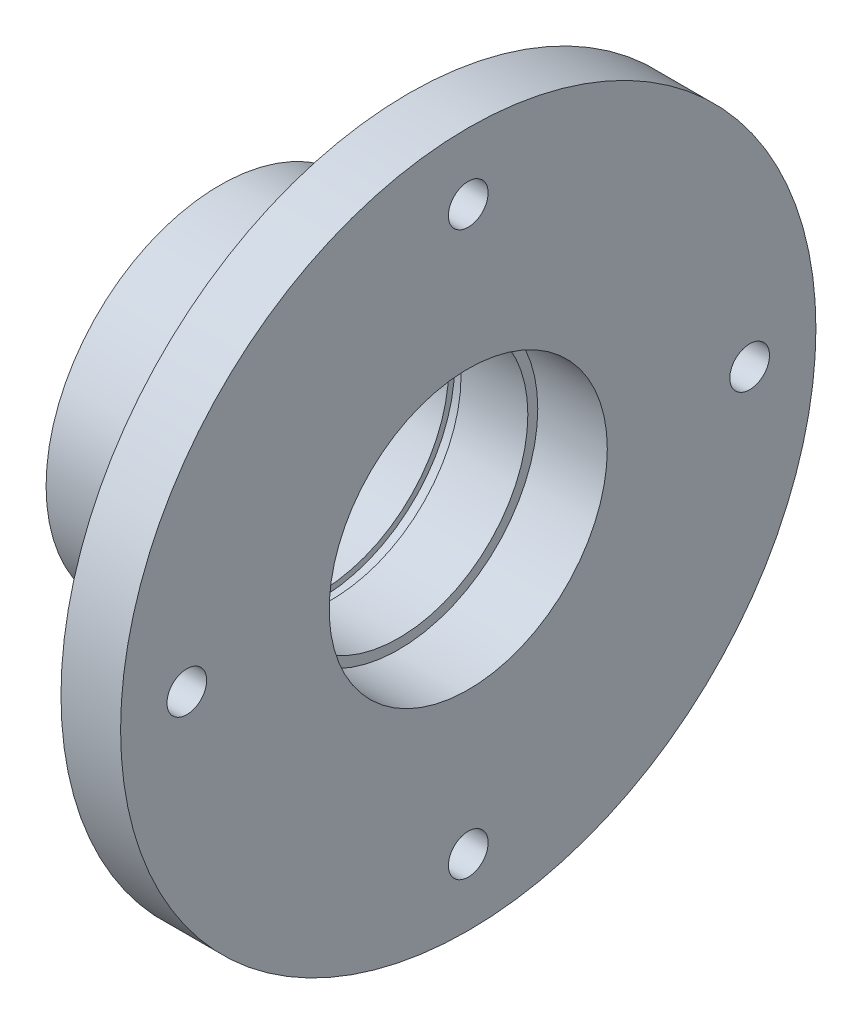
SolidWorks part; units mm, degrees
ref_plane "Front Plane" through (0, 0, 0) normal (0, 0, 1) x (1, 0, 0)
ref_plane "Top Plane" through (0, 0, 0) normal (0, 1, 0) x (1, 0, 0)
ref_plane "Right Plane" through (0, 0, 0) normal (1, 0, 0) x (0, 0, -1)
sketch "Sketch1" plane through (0, 0, 0) normal (1, 0, 0) x (0, 0, -1)
  circle A0 centre (0, 0) radius 35
extrude "Boss-Extrude1" add sketch "Sketch1" against normal blind 25
sketch "Sketch2" plane through (-25, 0, 0) normal (-1, 0, 0) x (0, 0, 1)
  circle A0 centre (0, 0) radius 17.5
  circle A1 centre (0, 0) radius 35
extrude "Cut-Extrude1" cut sketch "Sketch2" against normal blind 19
sketch "Sketch3" plane through (-6, 0, 0) normal (-1, 0, 0) x (0, 0, 1)
  circle A0 centre (0, 28.33) radius 2
  circle A1 centre (28.33, 0) radius 2
  circle A2 centre (0, -28.33) radius 2
  circle A3 centre (-28.33, 0) radius 2
  point P12 (0, 0)
  dimension "D1" = 28.33
  dimension "D2" = 4
extrude "Cut-Extrude2" cut sketch "Sketch3" against normal blind 18
sketch "Sketch4" plane through (-6, 0, 0) normal (-1, 0, 0) x (0, 0, 1)
  circle A0 centre (0, 28.33) radius 5.5
  circle A1 centre (28.33, 0) radius 5.5
  circle A2 centre (0, -28.33) radius 5.5
  circle A3 centre (-28.33, 0) radius 5.5
  point P12 (0, 0)
  dimension "D1" = 4
extrude "Cut-Extrude4" cut sketch "Sketch4" against normal blind 3
sketch "Sketch5" plane through (-25, 0, 0) normal (-1, 0, 0) x (0, 0, 1)
  circle A0 centre (0, 0) radius 9.5
extrude "Cut-Extrude5" cut sketch "Sketch5" against normal up to next
sketch "Sketch6" plane through (0, 0, 0) normal (1, 0, 0) x (0, 0, -1)
  circle A0 centre (0, 0) radius 13
  dimension "D1" = 26
extrude "Cut-Extrude6" cut sketch "Sketch6" against normal blind 20
ref_plane "Plane1" through (0, 17.5, 0) normal (0, 1, 0) x (1, 0, 0)
sketch "Sketch7" plane through (0, 17.5, 0) normal (0, 1, 0) x (1, 0, 0)
  line L0 (-25, 17.5) -> (-25, -17.5) construction
  circle A0 centre (-10, 0) radius 2.5
  dimension "D1" = 15
extrude "Cut-Extrude7" cut sketch "Sketch7" against normal up to next
sketch "Sketch8" plane through (0, 0, 0) normal (1, 0, 0) x (0, 0, -1)
  circle A0 centre (0, 0) radius 14
extrude "Cut-Extrude8" cut sketch "Sketch8" against normal blind 7
ref_plane "Plane2" through (-14.35, 0, 0) normal (1, 0, 0) x (0, 0, -1)
sketch "Sketch9" plane through (-14.35, 0, 0) normal (1, 0, 0) x (0, 0, -1)
  circle A0 centre (0, 0) radius 13.6
extrude "Cut-Extrude9" cut sketch "Sketch9" against normal mid plane 1.25
